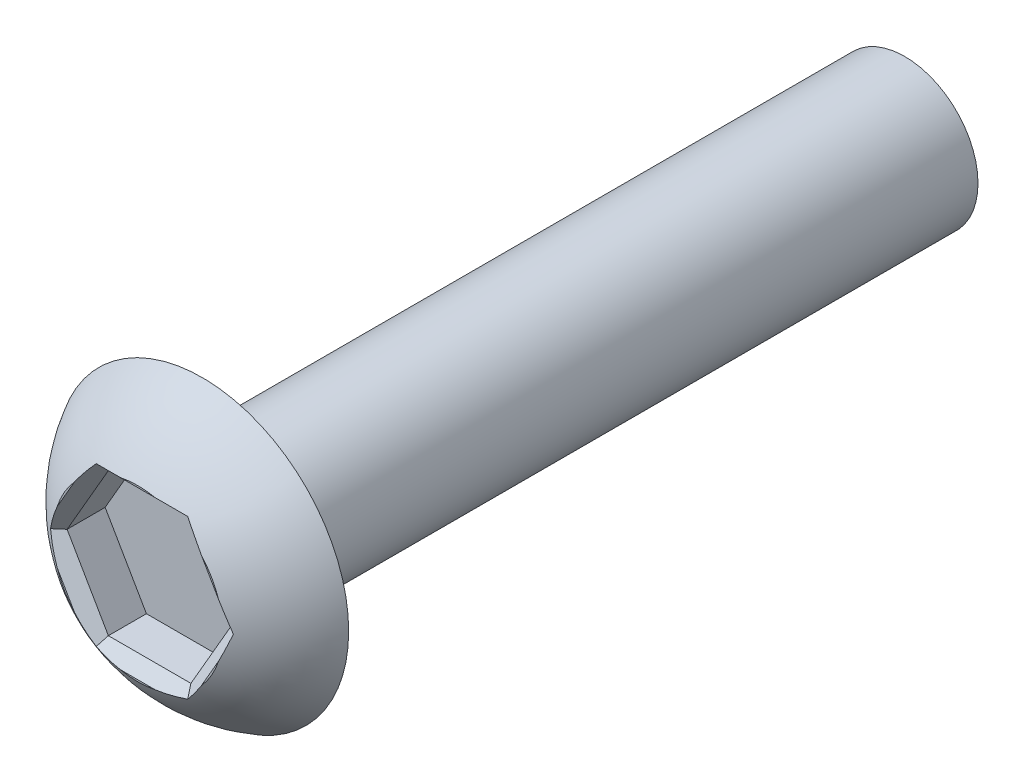
SolidWorks part; units mm, degrees
ref_plane "Front Plane" through (0, 0, 0) normal (0, 0, 1) x (1, 0, 0)
ref_plane "Top Plane" through (0, 0, 0) normal (0, 1, 0) x (1, 0, 0)
ref_plane "Right Plane" through (0, 0, 0) normal (1, 0, 0) x (0, 0, -1)
sketch "Sketch1" plane through (0, 0, 0) normal (0, 0, 1) x (1, 0, 0)
  circle A0 centre (0, 0) radius 1.25
extrude "Boss-Extrude1" add sketch "Sketch1" against normal blind 12
sketch "Sketch3" plane through (0, 0, 0) normal (1, 0, 0) x (0, 0, -1)
  line L0 (-1.5, 0) -> (-1.5, -2.0721)
  line L1 (0, 0) -> (0, 2.5)
  line L2 (-1.5, 0) -> (0, 0)
  arc A0 (-1.5, 0) -> (0, 2.5) centre (1.3333, 0) cw
  dimension "D1" = 1.5
  dimension "D2" = 2.5
revolve "Revolve1" add sketch "Sketch3" angle 360 about L2 region at (0, 0.9825, 0.6161)
sketch3d "3DSketch1" plane through (0, 0, 0) normal (0, 0, 1) x (1, 0, 0)
  dimension "D1" = 1.5
sketch "Sketch5" plane through (0, 0, 1.5) normal (0, 0, -1) x (-1, 0, 0)
  line L1 (-1.4099, 0) -> (-0.705, -1.221)
  line L2 (-0.705, -1.221) -> (0.705, -1.221)
  line L3 (0.705, -1.221) -> (1.4099, 0)
  line L4 (1.4099, 0) -> (0.705, 1.221)
  line L5 (0.705, 1.221) -> (-0.705, 1.221)
  line L6 (-0.705, 1.221) -> (-1.4099, 0)
  circle A0 centre (0, 0) radius 1.221 construction
extrude "Cut-Extrude1" cut sketch "Sketch5" along normal blind 1.25
sketch "Sketch6" plane through (0, 0, 0) normal (1, 0, 0) x (0, 0, -1)
  line L1 (-1.1, 2.3975) -> (-2.3497, 2.3975)
  line L2 (-1.1, 2.3975) -> (-1.1, -1.9866)
  line L3 (-1.1, -1.9866) -> (-2.3497, -1.9866)
  line L4 (-2.3497, 2.3975) -> (-2.3497, -1.9866)
  dimension "D1" = 1.1
extrude "Cut-Extrude2" cut sketch "Sketch6" against normal through all both and the other way through all
chamfer "Chamfer2" distance 0.2 angle 45 6 edges at (1.0574, 0.6105, 1.1) (1.0574, -0.6105, 1.1) (0, -1.221, 1.1) (-1.0574, -0.6105, 1.1) (0, 1.221, 1.1) (-1.0574, 0.6105, 1.1)
